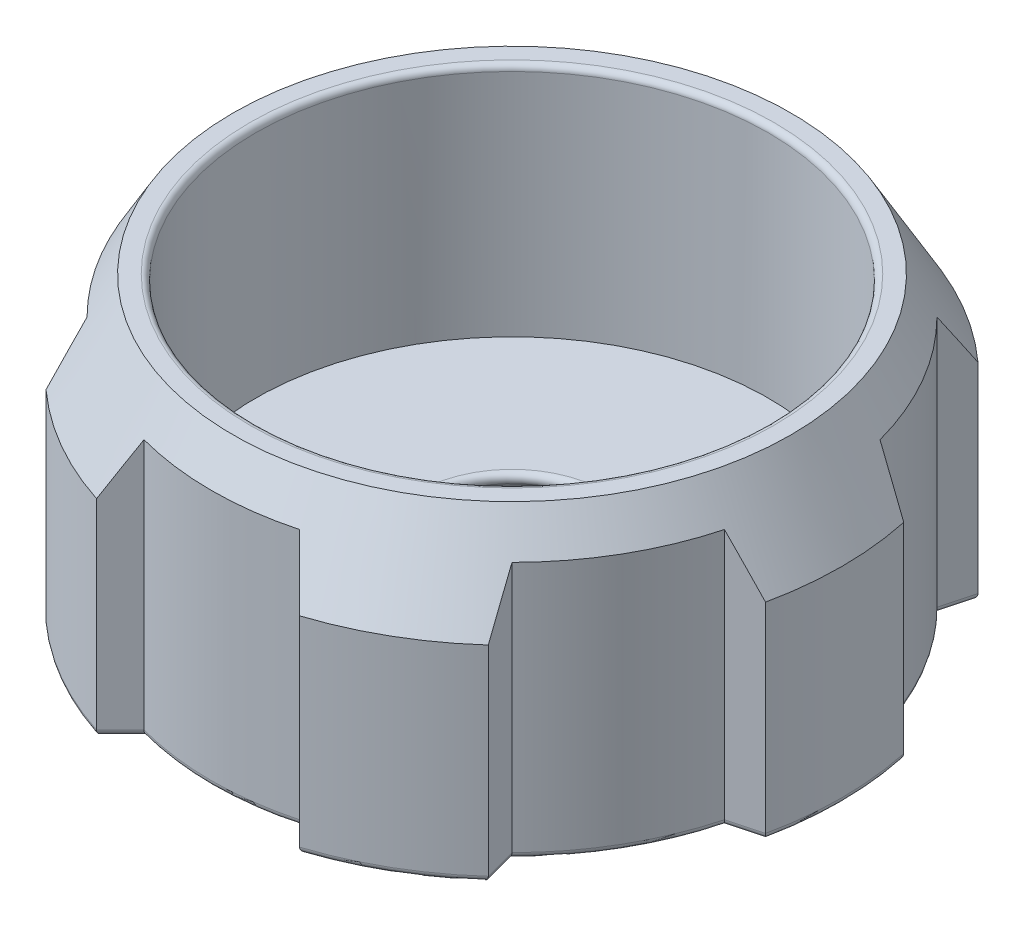
SolidWorks part; units mm, degrees
material "PET"
ref_plane "Front Plane" through (0, 0, 0) normal (0, 0, 1) x (1, 0, 0)
ref_plane "Top Plane" through (0, 0, 0) normal (0, 1, 0) x (1, 0, 0)
ref_plane "Right Plane" through (0, 0, 0) normal (1, 0, 0) x (0, 0, -1)
sketch "Sketch1" plane through (0, 0, 0) normal (0, 0, 1) x (1, 0, 0)
  line L0 (0, 0) -> (0, 12.4053) construction
  line L1 (20, 0) -> (14.2265, 10)
  line L2 (14.2265, 10) -> (43.5, 10)
  line L3 (43.5, 10) -> (43.5, 50)
  line L4 (43.5, 50) -> (47.3397, 50)
  line L5 (47.3397, 50) -> (56, 35)
  line L6 (56, 35) -> (56, 0)
  line L7 (56, 0) -> (20, 0)
  dimension "D1" = 40
  dimension "D2" = 60
  dimension "D3" = 87
  dimension "D4" = 112
  dimension "D5" = 10
  dimension "D6" = 30
  dimension "D7" = 40
  dimension "D8" = 15
revolve "body" add sketch "Sketch1" angle 360 about L0
sketch "Sketch5" plane through (0, 0, 0) normal (0, -1, 0) x (1, 0, 0)
  line L0 (49.2622, 13.1998) -> (54.7583, 11.7271)
  line L1 (36.0624, 36.0624) -> (37.5351, 41.5586)
  line L2 (0, 0) -> (56, 0) construction
  arc A0 (49.2622, 13.1998) -> (36.0624, 36.0624) centre (0, 0) ccw
  circle A1 centre (0, 0) radius 56 construction
  dimension "D3" = 5
  dimension "D1" = 30
  dimension "D2" = 90
  dimension "D4" = 15
extrude "side_cutout" cut sketch "Sketch5" against normal through all and the other way through all flip side to cut
pattern_circular "side_cutout_pattern" count 6 over 360 about axis through (0, 0, 0) along (0, -1, 0) of "side_cutout"
fillet "overall_fillets" radius 1 27 edges at (14.2265, 10, 0) (20, 0, 0) (43.5, 50, 0) (28, 0, -48.4974) (15.2115, 0, -51.2739) (0, 0, -51) (-15.2115, 0, -51.2739) (-28, 0, -48.4974) (-36.7988, 0, -38.8105) (-44.1673, 0, -25.5) (-52.0103, 0, -12.4634) (-56, 0, 0) (-52.0103, 0, 12.4634) (-44.1673, 0, 25.5) (-36.7988, 0, 38.8105) (-28, 0, 48.4974) (-15.2115, 0, 51.2739) (0, 0, 51) (15.2115, 0, 51.2739) (28, 0, 48.4974) (36.7988, 0, 38.8105) (44.1673, 0, 25.5) (52.0103, 0, 12.4634) (56, 0, 0) (52.0103, 0, -12.4634) (44.1673, 0, -25.5) (36.7988, 0, -38.8105)
sketch "screw_hole_pos" plane through (0, 0, 0) normal (0, -1, 0) x (1, 0, 0)
  point P0 (46, 0)
  dimension "D1" = 46
hole_wizard "screw_holes" positions "screw_hole_pos" profile "Sketch4" hole size "Ø2.7" standard "DIN"
sketch "Sketch4" plane through (46, 0, 0) normal (1, 0, 0) x (0, 0, -1)
  line L0 (0, 0) -> (0, 8.8112)
  line L1 (0, 8.8112) -> (1.35, 8)
  line L2 (1.35, 8) -> (1.35, 0.3)
  line L3 (1.35, 0.3) -> (1.65, 0)
  line L5 (1.65, 0) -> (0, 0)
  line L6 (-1.35, 0.3) -> (-1.65, 0) construction
  line L10 (0, 8.8112) -> (-1.35, 8) construction
  line L11 (0, -6.35) -> (0, 107.95) construction
  dimension "Hole Dia." = 2.7
  dimension "Hole Depth" = 8
  dimension "Near C'Sink Dia." = 3.3
  dimension "Near C'Sink Angle" = 90
  dimension "Drill Angle" = 118
pattern_circular "screw_hole_pattern" count 6 over 360 about axis through (0, 8.5, 0) along (0, 1, 0) of "screw_holes"
equation "\"paper_size\" = 600mm"
equation "\"cb_roll_d_outer\" = 86mm"
equation "\"cb_roll_d_inner\" = 76mm"
equation "\"attached_len\" = \"spring_l_max\" * 2 - \"spring_l_min\" + 18"
equation "\"helper_d\" = 92mm"
equation "\"outer_d\" = 112mm"
equation "\"spring_l_max\" = 25mm"
equation "\"spring_l_min\" = 10mm"
equation "\"cone_d_larger\" = 40mm"
equation "\"cone_angle\" = 60deg"
equation "\"D2@Sketch1\"=\"cone_angle\""
equation "\"D4@Sketch1\"=\"outer_d\""
equation "\"D3@Sketch1\"=\"cb_roll_d_outer\" + 1"
equation "\"D1@Sketch1\"=\"cone_d_larger\""
equation "\"bottom_screw_ring_d\" = 92mm"
equation "\"D1@screw_hole_pos\"=\"bottom_screw_ring_d\" / 2"
